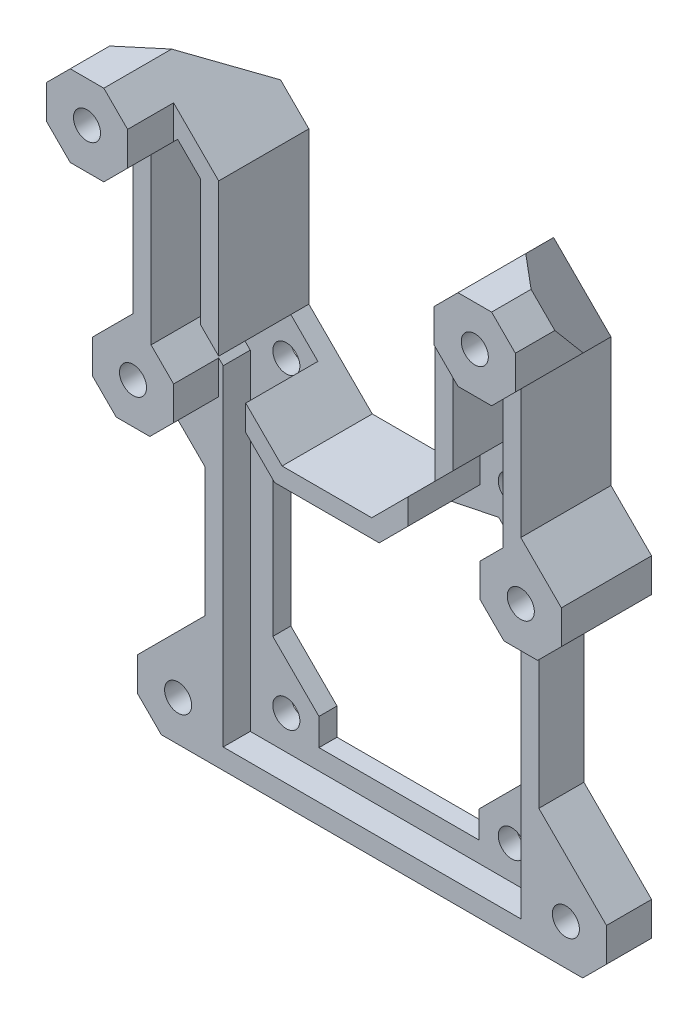
SolidWorks part; units mm, degrees
ref_plane "Front Plane" through (0, 0, 0) normal (0, 0, 1) x (1, 0, 0)
ref_plane "Top Plane" through (0, 0, 0) normal (0, 1, 0) x (1, 0, 0)
ref_plane "Right Plane" through (0, 0, 0) normal (1, 0, 0) x (0, 0, -1)
sketch "Sketch1" plane through (0, 0, 0) normal (0, 0, 1) x (1, 0, 0)
  line L0 (-21.5, 0) -> (21.5, 0) construction
  line L1 (21.5, 0) -> (21.5, 60) construction
  line L2 (21.5, 60) -> (-21.5, 60) construction
  line L3 (-21.5, 60) -> (-21.5, 0) construction
  line L4 (-21.5, 33) -> (21.5, 33) construction
  line L5 (0, 0) -> (0, 60) construction
  line L6 (-14, -2.1213) -> (-11, -2.1213)
  line L7 (-8.8787, 0) -> (-8.8787, 3)
  line L8 (-8.8787, 3) -> (-11, 5.1213)
  line L9 (-11, 5.1213) -> (-14, 5.1213)
  line L10 (-14, 5.1213) -> (-16.1213, 3)
  line L11 (-16.1213, 3) -> (-16.1213, 0)
  line L12 (-16.1213, 0) -> (-14, -2.1213)
  line L13 (-11, -2.1213) -> (-8.8787, 0)
  line L14 (-4.9706, 33) -> (-21.5, 49.5294) construction
  line L15 (8.8787, 0) -> (11, -2.1213)
  line L16 (11, -2.1213) -> (14, -2.1213)
  line L17 (14, -2.1213) -> (16.1213, 0)
  line L18 (16.1213, 0) -> (16.1213, 3)
  line L19 (16.1213, 3) -> (14, 5.1213)
  line L20 (14, 5.1213) -> (11, 5.1213)
  line L21 (11, 5.1213) -> (8.8787, 3)
  line L22 (8.8787, 3) -> (8.8787, 0)
  line L23 (-9, 34.1299) -> (-9, 37.0294)
  line L24 (-9, 37.0294) -> (-11.0503, 39.0797)
  line L25 (-11.0503, 39.0797) -> (-13.9497, 39.0797)
  line L26 (-13.9497, 39.0797) -> (-16, 37.0294)
  line L27 (-16, 37.0294) -> (-16, 34.1299)
  line L28 (-16, 34.1299) -> (-13.9497, 32.0797)
  line L29 (-13.9497, 32.0797) -> (-11.0503, 32.0797)
  line L30 (-11.0503, 32.0797) -> (-9, 34.1299)
  line L31 (9, 34.1299) -> (11.0503, 32.0797)
  line L32 (11.0503, 32.0797) -> (13.9497, 32.0797)
  line L33 (13.9497, 32.0797) -> (16, 34.1299)
  line L34 (16, 34.1299) -> (16, 37.0294)
  line L35 (16, 37.0294) -> (13.9497, 39.0797)
  line L36 (13.9497, 39.0797) -> (11.0503, 39.0797)
  line L37 (11.0503, 39.0797) -> (9, 37.0294)
  line L38 (9, 37.0294) -> (9, 34.1299)
  line L39 (-14, 0) -> (-14, 42.0294) construction
  line L40 (-16.5, 0) -> (-16.5, 44.5294) construction
  line L41 (-17, 58.136) -> (-17, 61.864)
  line L42 (-17, 61.864) -> (-19.636, 64.5)
  line L43 (-19.636, 64.5) -> (-23.364, 64.5)
  line L44 (-23.364, 64.5) -> (-26, 61.864)
  line L45 (-26, 61.864) -> (-26, 58.136)
  line L46 (-26, 58.136) -> (-23.364, 55.5)
  line L47 (-23.364, 55.5) -> (-19.636, 55.5)
  line L48 (-19.636, 55.5) -> (-17, 58.136)
  line L49 (-23.364, 37.5) -> (-26, 34.864)
  line L50 (-26, 34.864) -> (-26, 31.136)
  line L51 (-26, 31.136) -> (-23.364, 28.5)
  line L52 (-23.364, 28.5) -> (-19.636, 28.5)
  line L53 (-19.636, 28.5) -> (-17, 31.136)
  line L54 (-17, 31.136) -> (-17, 34.864)
  line L55 (-17, 34.864) -> (-19.636, 37.5)
  line L56 (-19.636, 37.5) -> (-23.364, 37.5)
  line L57 (-23.364, 4.5) -> (-26, 1.864)
  line L58 (-26, 1.864) -> (-26, -1.864)
  line L59 (-26, -1.864) -> (-23.364, -4.5)
  line L60 (-23.364, -4.5) -> (-19.636, -4.5)
  line L61 (-19.636, -4.5) -> (-17, -1.864)
  line L62 (-17, -1.864) -> (-17, 1.864)
  line L63 (-17, 1.864) -> (-19.636, 4.5)
  line L64 (-19.636, 4.5) -> (-23.364, 4.5)
  line L65 (23.364, -4.5) -> (26, -1.864)
  line L66 (26, -1.864) -> (26, 1.864)
  line L67 (26, 1.864) -> (23.364, 4.5)
  line L68 (23.364, 4.5) -> (19.636, 4.5)
  line L69 (19.636, 4.5) -> (17, 1.864)
  line L70 (17, 1.864) -> (17, -1.864)
  line L71 (17, -1.864) -> (19.636, -4.5)
  line L72 (19.636, -4.5) -> (23.364, -4.5)
  line L73 (19.636, 28.5) -> (23.364, 28.5)
  line L74 (23.364, 28.5) -> (26, 31.136)
  line L75 (26, 31.136) -> (26, 34.864)
  line L76 (26, 34.864) -> (23.364, 37.5)
  line L77 (23.364, 37.5) -> (19.636, 37.5)
  line L78 (19.636, 37.5) -> (17, 34.864)
  line L79 (17, 34.864) -> (17, 31.136)
  line L80 (17, 31.136) -> (19.636, 28.5)
  line L81 (23.364, 64.5) -> (19.636, 64.5)
  line L82 (19.636, 64.5) -> (17, 61.864)
  line L83 (17, 61.864) -> (17, 58.136)
  line L84 (17, 58.136) -> (19.636, 55.5)
  line L85 (19.636, 55.5) -> (23.364, 55.5)
  line L86 (23.364, 55.5) -> (26, 58.136)
  line L87 (26, 58.136) -> (26, 61.864)
  line L88 (26, 61.864) -> (23.364, 64.5)
  line L89 (-12, 45) -> (-12, 71.0139) construction
  line L90 (12, 45) -> (12, 71.0139) construction
  line L91 (0, -4.5) -> (-19.636, -4.5)
  line L92 (0, 0) -> (-8.8787, 0)
  line L94 (0, -2.25) -> (-16.5, -2.25)
  line L95 (-16.5, -2.25) -> (-16.5, 34.364)
  line L96 (-9, 37.0294) -> (-4.9706, 33)
  line L97 (0, -4.5) -> (0, 0) construction
  line L98 (0, 33) -> (-4.9706, 33)
  line L100 (-5.799, 31) -> (0, 31)
  line L101 (0, -2.25) -> (-16.5, -2.25) construction
  line L102 (-17, 61.864) -> (-12, 56.864)
  line L103 (-12, 56.864) -> (-12, 40.0294)
  line L104 (-12, 40.0294) -> (-11.0503, 39.0797)
  line L105 (-11.0503, 39.0797) -> (-12, 40.0294)
  line L106 (-23.364, 55.5) -> (-21.5, 53.636)
  line L107 (-23.364, 37.5) -> (-21.5, 39.364)
  line L108 (-21.5, 39.364) -> (-21.5, 53.636)
  line L109 (-23.364, 4.5) -> (-18.5, 9.364)
  line L110 (-18.5, 9.364) -> (-18.5, 23.636)
  line L111 (-18.5, 23.636) -> (-23.364, 28.5)
  line L112 (-11.0503, 32.0797) -> (-14, 29.1299)
  line L113 (-14, 29.1299) -> (-14, 8.1213)
  line L114 (-14, 8.1213) -> (-11, 5.1213)
  line L115 (-16.5, -4.5) -> (-16.5, 0) construction
  line L116 (-16.5503, 58.5858) -> (-14, 56.0355)
  line L117 (-14, 56.0355) -> (-14, 42.0294)
  line L118 (-14, 42.0294) -> (-12, 40.0294)
  line L119 (-17, 34.864) -> (-16.5, 34.364)
  line L120 (-19.636, 37.5) -> (-19.5, 37.364)
  line L121 (-19.5, 37.364) -> (-19.5, 55.636)
  line L122 (-19.5, 55.636) -> (-19.636, 55.5)
  line L123 (-17, 58.136) -> (-16.5503, 58.5858)
  line L124 (-19.636, 55.5) -> (-19.5, 55.636)
  line L125 (-9, 34.201) -> (-5.799, 31)
  line L126 (-9, 34.1299) -> (-8.9645, 34.1655)
  line L127 (-11.0503, 32.0797) -> (-5.799, 31)
  line L128 (-12, 50.5) -> (-33.4283, 71.9283) construction
  circle A0 centre (-21.5, 60) radius 1.5
  circle A1 centre (-21.5, 33) radius 1.5
  circle A2 centre (-21.5, 0) radius 1.5
  circle A3 centre (21.5, 0) radius 1.5
  circle A4 centre (21.5, 33) radius 1.5
  circle A5 centre (21.5, 60) radius 1.5
  circle A6 centre (-12.5, 1.5) radius 1.5
  circle A7 centre (12.5, 1.5) radius 1.5
  circle A8 centre (-12.5, 35.5797) radius 1.5
  circle A9 centre (12.5, 35.5797) radius 1.5
  circle A10 centre (0, 45) radius 12 construction
  circle A11 centre (-12.5, 1.5) radius 3.6213 construction
  circle A12 centre (12.5, 1.5) radius 3.6213 construction
  circle A13 centre (-12.5, 35.5797) radius 3.5 construction
  circle A14 centre (12.5, 35.5797) radius 3.5 construction
  circle A15 centre (-21.5, 60) radius 4.5 construction
  circle A16 centre (-21.5, 33) radius 4.5 construction
  circle A17 centre (-21.5, 0) radius 4.5 construction
  circle A18 centre (21.5, 0) radius 4.5 construction
  circle A19 centre (21.5, 33) radius 4.5 construction
  circle A20 centre (21.5, 60) radius 4.5 construction
  dimension "D4" = 3
  dimension "D5" = 24
  dimension "D7" = 45
  dimension "D8" = 7
  dimension "D9" = 9
  dimension "D10" = 9
  dimension "D11" = 9
  dimension "D12" = 9
  dimension "D13" = 9
  dimension "D14" = 9
  dimension "D1" = 43
  dimension "D2" = 33
  dimension "D3" = 27
  dimension "D6" = 12.5
  dimension "D15" = 2.5
  dimension "D16" = 2
  dimension "D17" = 2
  dimension "D18" = 45
  dimension "D19" = 45
  dimension "D20" = 2.25
  dimension "D21" = 2
  dimension "D22" = 2
  dimension "D23" = 2
  dimension "D24" = 2
sketch "Sketch5" plane through (0, 0, 0) normal (0, 0, 1) x (1, 0, 0)
  line L0 (0, -4.5) -> (-19.636, -4.5) construction
  line L1 (-23.364, -4.5) -> (-19.636, -4.5) construction
  line L2 (-26, -1.864) -> (-23.364, -4.5) construction
  line L3 (-26, 1.864) -> (-26, -1.864) construction
  line L4 (-23.364, 4.5) -> (-26, 1.864) construction
  line L5 (-23.364, 4.5) -> (-18.5, 9.364) construction
  line L6 (-18.5, 9.364) -> (-18.5, 23.636) construction
  line L7 (-18.5, 23.636) -> (-23.364, 28.5) construction
  line L8 (-26, 31.136) -> (-23.364, 28.5) construction
  line L9 (-26, 34.864) -> (-26, 31.136) construction
  line L10 (-23.364, 37.5) -> (-26, 34.864) construction
  line L11 (-23.364, 37.5) -> (-21.5, 39.364) construction
  line L12 (-21.5, 39.364) -> (-21.5, 53.636) construction
  line L13 (-23.364, 55.5) -> (-21.5, 53.636) construction
  line L14 (-26, 58.136) -> (-23.364, 55.5) construction
  line L15 (-26, 61.864) -> (-26, 58.136) construction
  line L16 (-23.364, 64.5) -> (-26, 61.864) construction
  line L17 (-19.636, 64.5) -> (-23.364, 64.5) construction
  line L18 (-17, 61.864) -> (-19.636, 64.5) construction
  line L19 (-17, 61.864) -> (-12, 56.864) construction
  line L20 (-12, 56.864) -> (-12, 40.0294) construction
  line L21 (-12, 40.0294) -> (-11.0503, 39.0797) construction
  line L22 (-9, 37.0294) -> (-11.0503, 39.0797) construction
  line L23 (-9, 37.0294) -> (-4.9706, 33) construction
  line L24 (0, 33) -> (-4.9706, 33) construction
  line L25 (-5.799, 31) -> (0, 31) construction
  line L26 (-11.0503, 32.0797) -> (-5.799, 31) construction
  line L28 (-11.0503, 32.0797) -> (-14, 29.1299) construction
  line L29 (-14, 29.1299) -> (-14, 8.1213) construction
  line L30 (-14, 8.1213) -> (-11, 5.1213) construction
  line L31 (-8.8787, 3) -> (-11, 5.1213) construction
  line L32 (-8.8787, 0) -> (-8.8787, 3) construction
  line L33 (0, 0) -> (-8.8787, 0) construction
  line L34 (0, 0) -> (0, 60) construction
  line L35 (0, -4.5) -> (0, 0) construction
  line L36 (19.636, -4.5) -> (-19.636, -4.5)
  line L37 (-23.364, -4.5) -> (-19.636, -4.5)
  line L38 (-26, -1.864) -> (-23.364, -4.5)
  line L39 (-26, 1.864) -> (-26, -1.864)
  line L40 (-23.364, 4.5) -> (-26, 1.864)
  line L41 (-23.364, 4.5) -> (-18.5, 9.364)
  line L42 (-18.5, 9.364) -> (-18.5, 23.636)
  line L43 (-18.5, 23.636) -> (-23.364, 28.5)
  line L44 (-26, 31.136) -> (-23.364, 28.5)
  line L45 (-26, 34.864) -> (-26, 31.136)
  line L46 (-23.364, 37.5) -> (-26, 34.864)
  line L47 (-23.364, 37.5) -> (-21.5, 39.364)
  line L48 (-21.5, 39.364) -> (-21.5, 53.636)
  line L49 (-23.364, 55.5) -> (-21.5, 53.636)
  line L50 (-26, 58.136) -> (-23.364, 55.5)
  line L51 (-26, 61.864) -> (-26, 58.136)
  line L52 (-23.364, 64.5) -> (-26, 61.864)
  line L53 (-19.636, 64.5) -> (-23.364, 64.5)
  line L54 (-17, 61.864) -> (-19.636, 64.5)
  line L55 (-17, 61.864) -> (-12, 56.864)
  line L56 (-12, 56.864) -> (-12, 40.0294)
  line L57 (-12, 40.0294) -> (-11.0503, 39.0797)
  line L58 (-9, 37.0294) -> (-11.0503, 39.0797)
  line L59 (-9, 37.0294) -> (-4.9706, 33)
  line L60 (4.9706, 33) -> (-4.9706, 33)
  line L61 (-5.799, 31) -> (5.799, 31)
  line L63 (11.0503, 32.0797) -> (5.799, 31)
  line L64 (-11.0503, 32.0797) -> (-14, 29.1299)
  line L65 (-14, 29.1299) -> (-14, 8.1213)
  line L66 (-14, 8.1213) -> (-11, 5.1213)
  line L67 (-8.8787, 3) -> (-11, 5.1213)
  line L68 (-8.8787, 0) -> (-8.8787, 3)
  line L69 (8.8787, 0) -> (-8.8787, 0)
  line L70 (0, 0) -> (0, 60) construction
  line L71 (0, -4.5) -> (0, 0) construction
  line L72 (8.8787, 0) -> (8.8787, 3)
  line L73 (8.8787, 3) -> (11, 5.1213)
  line L74 (14, 8.1213) -> (11, 5.1213)
  line L75 (14, 29.1299) -> (14, 8.1213)
  line L76 (11.0503, 32.0797) -> (14, 29.1299)
  line L79 (9, 37.0294) -> (4.9706, 33)
  line L80 (9, 37.0294) -> (11.0503, 39.0797)
  line L81 (12, 40.0294) -> (11.0503, 39.0797)
  line L82 (12, 56.864) -> (12, 40.0294)
  line L83 (17, 61.864) -> (12, 56.864)
  line L84 (17, 61.864) -> (19.636, 64.5)
  line L85 (19.636, 64.5) -> (23.364, 64.5)
  line L86 (23.364, 64.5) -> (26, 61.864)
  line L87 (26, 61.864) -> (26, 58.136)
  line L88 (26, 58.136) -> (23.364, 55.5)
  line L89 (23.364, 55.5) -> (21.5, 53.636)
  line L90 (21.5, 39.364) -> (21.5, 53.636)
  line L91 (23.364, 37.5) -> (21.5, 39.364)
  line L92 (23.364, 37.5) -> (26, 34.864)
  line L93 (26, 34.864) -> (26, 31.136)
  line L94 (26, 31.136) -> (23.364, 28.5)
  line L95 (18.5, 23.636) -> (23.364, 28.5)
  line L96 (18.5, 9.364) -> (18.5, 23.636)
  line L97 (23.364, 4.5) -> (18.5, 9.364)
  line L98 (23.364, 4.5) -> (26, 1.864)
  line L99 (26, 1.864) -> (26, -1.864)
  line L100 (26, -1.864) -> (23.364, -4.5)
  line L101 (23.364, -4.5) -> (19.636, -4.5)
  line L106 (-11.0503, 32.0797) -> (-5.799, 31)
  circle A0 centre (-12.5, 35.5797) radius 1.5 construction
  circle A1 centre (-12.5, 1.5) radius 1.5 construction
  circle A2 centre (12.5, 1.5) radius 1.5 construction
  circle A3 centre (12.5, 35.5797) radius 1.5 construction
  circle A4 centre (-12.5, 35.5797) radius 1.5
  circle A5 centre (-12.5, 1.5) radius 1.5
  circle A6 centre (12.5, 1.5) radius 1.5
  circle A7 centre (12.5, 35.5797) radius 1.5
extrude "Boss-Extrude1" add sketch "Sketch5" along normal blind 2
sketch "Sketch9" plane through (0, 0, 2) normal (0, 0, 1) x (1, 0, 0)
  line L0 (0, -4.5) -> (-19.636, -4.5) construction
  line L1 (-23.364, -4.5) -> (-19.636, -4.5) construction
  line L2 (-26, -1.864) -> (-23.364, -4.5) construction
  line L3 (-26, 1.864) -> (-26, -1.864) construction
  line L4 (-23.364, 4.5) -> (-26, 1.864) construction
  line L5 (-23.364, 4.5) -> (-18.5, 9.364) construction
  line L6 (-18.5, 9.364) -> (-18.5, 23.636) construction
  line L7 (-18.5, 23.636) -> (-23.364, 28.5) construction
  line L8 (-26, 31.136) -> (-23.364, 28.5) construction
  line L9 (-26, 34.864) -> (-26, 31.136) construction
  line L10 (-23.364, 37.5) -> (-26, 34.864) construction
  line L11 (-23.364, 37.5) -> (-21.5, 39.364) construction
  line L12 (-21.5, 39.364) -> (-21.5, 53.636) construction
  line L13 (-23.364, 55.5) -> (-21.5, 53.636) construction
  line L14 (-26, 58.136) -> (-23.364, 55.5) construction
  line L15 (-26, 61.864) -> (-26, 58.136) construction
  line L16 (-23.364, 64.5) -> (-26, 61.864) construction
  line L17 (-19.636, 64.5) -> (-23.364, 64.5) construction
  line L18 (-17, 61.864) -> (-19.636, 64.5) construction
  line L19 (-17, 61.864) -> (-12, 56.864) construction
  line L20 (-12, 56.864) -> (-12, 40.0294) construction
  line L21 (-14, 42.0294) -> (-12, 40.0294) construction
  line L22 (-14, 56.0355) -> (-14, 42.0294) construction
  line L24 (-16.5, -2.25) -> (-16.5, 34.364) construction
  line L25 (0, -2.25) -> (-16.5, -2.25) construction
  line L26 (0, 33) -> (-4.9706, 33) construction
  line L30 (-5.799, 31) -> (0, 31) construction
  line L31 (0, 0) -> (0, 60) construction
  line L32 (0, -4.5) -> (0, 0) construction
  line L33 (19.636, -4.5) -> (-19.636, -4.5)
  line L34 (-23.364, -4.5) -> (-19.636, -4.5)
  line L35 (-26, -1.864) -> (-23.364, -4.5)
  line L36 (-26, 1.864) -> (-26, -1.864)
  line L37 (-23.364, 4.5) -> (-26, 1.864)
  line L38 (-23.364, 4.5) -> (-18.5, 9.364)
  line L39 (-18.5, 9.364) -> (-18.5, 23.636)
  line L40 (-18.5, 23.636) -> (-23.364, 28.5)
  line L41 (-26, 31.136) -> (-23.364, 28.5)
  line L42 (-26, 34.864) -> (-26, 31.136)
  line L43 (-23.364, 37.5) -> (-26, 34.864)
  line L44 (-23.364, 37.5) -> (-21.5, 39.364)
  line L45 (-21.5, 39.364) -> (-21.5, 53.636)
  line L46 (-23.364, 55.5) -> (-21.5, 53.636)
  line L47 (-26, 58.136) -> (-23.364, 55.5)
  line L48 (-26, 61.864) -> (-26, 58.136)
  line L49 (-23.364, 64.5) -> (-26, 61.864)
  line L50 (-19.636, 64.5) -> (-23.364, 64.5)
  line L51 (-17, 61.864) -> (-19.636, 64.5)
  line L52 (-17, 61.864) -> (-12, 56.864)
  line L53 (-12, 56.864) -> (-12, 40.0294)
  line L54 (-14, 42.0294) -> (-12, 40.0294)
  line L55 (-14, 56.0355) -> (-14, 42.0294)
  line L56 (-17, 34.864) -> (-16.5, 34.364) construction
  line L57 (-17, 34.864) -> (-19.636, 37.5) construction
  line L58 (16.5, -2.25) -> (-16.5, -2.25)
  line L59 (-9, 37.0294) -> (-4.9706, 33) construction
  line L60 (-9, 34.1299) -> (-9, 37.0294) construction
  line L62 (4.9706, 33) -> (-4.9706, 33)
  line L63 (-9, 37.0294) -> (-4.9706, 33)
  line L64 (0, 0) -> (0, 60) construction
  line L65 (0, -4.5) -> (0, 0) construction
  line L66 (19.636, 64.5) -> (23.364, 64.5)
  line L67 (-9, 34.201) -> (-9, 37.0294)
  line L68 (9, 34.201) -> (5.799, 31)
  line L69 (-5.799, 31) -> (5.799, 31)
  line L70 (16.5, -2.25) -> (16.5, 34.364)
  line L72 (14, 56.0355) -> (14, 42.0294)
  line L73 (14, 42.0294) -> (12, 40.0294)
  line L74 (12, 56.864) -> (12, 40.0294)
  line L75 (17, 61.864) -> (12, 56.864)
  line L76 (17, 61.864) -> (19.636, 64.5)
  line L77 (23.364, 64.5) -> (26, 61.864)
  line L78 (26, 61.864) -> (26, 58.136)
  line L79 (26, 58.136) -> (23.364, 55.5)
  line L80 (23.364, 55.5) -> (21.5, 53.636)
  line L81 (21.5, 39.364) -> (21.5, 53.636)
  line L82 (23.364, 37.5) -> (21.5, 39.364)
  line L83 (23.364, 37.5) -> (26, 34.864)
  line L84 (26, 34.864) -> (26, 31.136)
  line L85 (26, 31.136) -> (23.364, 28.5)
  line L86 (18.5, 23.636) -> (23.364, 28.5)
  line L87 (18.5, 9.364) -> (18.5, 23.636)
  line L88 (23.364, 4.5) -> (18.5, 9.364)
  line L89 (23.364, 4.5) -> (26, 1.864)
  line L90 (26, 1.864) -> (26, -1.864)
  line L91 (26, -1.864) -> (23.364, -4.5)
  line L92 (23.364, -4.5) -> (19.636, -4.5)
  line L93 (9, 34.201) -> (9, 37.0294)
  line L94 (17, 34.864) -> (16.5, 34.364)
  line L95 (9, 37.0294) -> (4.9706, 33)
  line L96 (-19.5, 37.364) -> (-19.5, 55.636) construction
  line L98 (-19.636, 55.5) -> (-17, 58.136) construction
  line L99 (-17, 58.136) -> (-16.5503, 58.5858) construction
  line L100 (-16.5503, 58.5858) -> (-14, 56.0355) construction
  line L101 (-9, 34.201) -> (-5.799, 31) construction
  line L102 (-16.5, -2.25) -> (-16.5, 34.364)
  line L103 (-17, 34.864) -> (-16.5, 34.364)
  line L104 (-17, 34.864) -> (-19.5, 37.364)
  line L106 (-19.5, 37.364) -> (-19.5, 55.636)
  line L108 (-19.5, 55.636) -> (-17, 58.136)
  line L109 (-17, 58.136) -> (-16.5503, 58.5858)
  line L110 (-16.5503, 58.5858) -> (-14, 56.0355)
  line L111 (-9, 34.201) -> (-5.799, 31)
  line L112 (17, 34.864) -> (19.5, 37.364)
  line L114 (19.5, 37.364) -> (19.5, 55.636)
  line L116 (19.5, 55.636) -> (17, 58.136)
  line L117 (17, 58.136) -> (16.5503, 58.5858)
  line L118 (16.5503, 58.5858) -> (14, 56.0355)
  circle A0 centre (-21.5, 0) radius 1.5 construction
  circle A1 centre (-21.5, 33) radius 1.5 construction
  circle A3 centre (-21.5, 0) radius 1.5
  circle A4 centre (-21.5, 33) radius 1.5
  circle A7 centre (21.5, 33) radius 1.5
  circle A8 centre (21.5, 0) radius 1.5
extrude "Boss-Extrude3" add sketch "Sketch9" along normal blind 3
sketch "Sketch10" plane through (0, 0, 5) normal (0, 0, 1) x (1, 0, 0)
  line L0 (-23.364, 28.5) -> (-19.636, 28.5) construction
  line L1 (-26, 31.136) -> (-23.364, 28.5) construction
  line L2 (-26, 34.864) -> (-26, 31.136) construction
  line L3 (-23.364, 37.5) -> (-26, 34.864) construction
  line L4 (-23.364, 37.5) -> (-21.5, 39.364) construction
  line L5 (-21.5, 39.364) -> (-21.5, 53.636) construction
  line L6 (-23.364, 55.5) -> (-21.5, 53.636) construction
  line L7 (-26, 58.136) -> (-23.364, 55.5) construction
  line L8 (-26, 61.864) -> (-26, 58.136) construction
  line L9 (-23.364, 64.5) -> (-26, 61.864) construction
  line L10 (-19.636, 64.5) -> (-23.364, 64.5) construction
  line L11 (-17, 61.864) -> (-19.636, 64.5) construction
  line L12 (-17, 61.864) -> (-12, 56.864) construction
  line L13 (-12, 56.864) -> (-12, 40.0294) construction
  line L14 (-14, 42.0294) -> (-12, 40.0294) construction
  line L15 (-14, 56.0355) -> (-14, 42.0294) construction
  line L16 (-16.5503, 58.5858) -> (-14, 56.0355) construction
  line L17 (-17, 58.136) -> (-16.5503, 58.5858) construction
  line L18 (-19.636, 55.5) -> (-17, 58.136) construction
  line L20 (-19.5, 37.364) -> (-19.5, 55.636) construction
  line L22 (-17, 34.864) -> (-19.636, 37.5) construction
  line L23 (-17, 31.136) -> (-17, 34.864) construction
  line L24 (-19.636, 28.5) -> (-17, 31.136) construction
  line L25 (-9, 34.1299) -> (-9, 37.0294) construction
  line L26 (-9, 37.0294) -> (-4.9706, 33) construction
  line L27 (0, 33) -> (-4.9706, 33) construction
  line L28 (-5.799, 31) -> (0, 31) construction
  line L29 (-9, 34.201) -> (-5.799, 31) construction
  line L30 (-23.364, 28.5) -> (-19.636, 28.5)
  line L31 (-26, 31.136) -> (-23.364, 28.5)
  line L32 (-26, 34.864) -> (-26, 31.136)
  line L33 (-23.364, 37.5) -> (-26, 34.864)
  line L34 (-23.364, 37.5) -> (-21.5, 39.364)
  line L35 (-21.5, 39.364) -> (-21.5, 53.636)
  line L36 (-23.364, 55.5) -> (-21.5, 53.636)
  line L37 (-26, 58.136) -> (-23.364, 55.5)
  line L38 (-26, 61.864) -> (-26, 58.136)
  line L39 (-23.364, 64.5) -> (-26, 61.864)
  line L40 (-19.636, 64.5) -> (-23.364, 64.5)
  line L41 (-17, 61.864) -> (-19.636, 64.5)
  line L42 (-17, 61.864) -> (-12, 56.864)
  line L43 (-12, 56.864) -> (-12, 40.0294)
  line L44 (-14, 42.0294) -> (-12, 40.0294)
  line L45 (-14, 56.0355) -> (-14, 42.0294)
  line L46 (-16.5503, 58.5858) -> (-14, 56.0355)
  line L47 (-17, 58.136) -> (-16.5503, 58.5858)
  line L48 (-19.5, 55.636) -> (-17, 58.136)
  line L50 (-19.5, 37.364) -> (-19.5, 55.636)
  line L52 (-17, 34.864) -> (-19.5, 37.364)
  line L53 (-17, 31.136) -> (-17, 34.864)
  line L54 (-19.636, 28.5) -> (-17, 31.136)
  line L55 (-9, 34.201) -> (-9, 37.0294)
  line L56 (-9, 37.0294) -> (-4.9706, 33)
  line L57 (4.9706, 33) -> (-4.9706, 33)
  line L58 (-5.799, 31) -> (5.799, 31)
  line L59 (-9, 34.201) -> (-5.799, 31)
  line L60 (0, 0) -> (0, 60) construction
  line L61 (0, 0) -> (0, 60) construction
  line L62 (9, 34.201) -> (5.799, 31)
  line L63 (9, 37.0294) -> (4.9706, 33)
  line L64 (9, 34.201) -> (9, 37.0294)
  line L65 (19.636, 28.5) -> (17, 31.136)
  line L66 (17, 31.136) -> (17, 34.864)
  line L67 (17, 34.864) -> (19.5, 37.364)
  line L69 (19.5, 37.364) -> (19.5, 55.636)
  line L71 (19.5, 55.636) -> (17, 58.136)
  line L72 (17, 58.136) -> (16.5503, 58.5858)
  line L73 (16.5503, 58.5858) -> (14, 56.0355)
  line L74 (14, 56.0355) -> (14, 42.0294)
  line L75 (14, 42.0294) -> (12, 40.0294)
  line L76 (12, 56.864) -> (12, 40.0294)
  line L77 (17, 61.864) -> (12, 56.864)
  line L78 (17, 61.864) -> (19.636, 64.5)
  line L79 (19.636, 64.5) -> (23.364, 64.5)
  line L80 (23.364, 64.5) -> (26, 61.864)
  line L81 (26, 61.864) -> (26, 58.136)
  line L82 (26, 58.136) -> (23.364, 55.5)
  line L83 (23.364, 55.5) -> (21.5, 53.636)
  line L84 (21.5, 39.364) -> (21.5, 53.636)
  line L85 (23.364, 37.5) -> (21.5, 39.364)
  line L86 (23.364, 37.5) -> (26, 34.864)
  line L87 (26, 34.864) -> (26, 31.136)
  line L88 (26, 31.136) -> (23.364, 28.5)
  line L89 (23.364, 28.5) -> (19.636, 28.5)
  circle A0 centre (-21.5, 33) radius 1.5 construction
  circle A2 centre (-21.5, 33) radius 1.5
  circle A5 centre (21.5, 33) radius 1.5
extrude "Boss-Extrude4" add sketch "Sketch10" along normal blind 5
sketch "Sketch12" plane through (0, 0, 10) normal (0, 0, 1) x (1, 0, 0)
  line L0 (-26, 58.136) -> (-23.364, 55.5) construction
  line L1 (-26, 61.864) -> (-26, 58.136) construction
  line L2 (-23.364, 64.5) -> (-26, 61.864) construction
  line L3 (-19.636, 64.5) -> (-23.364, 64.5) construction
  line L4 (-17, 61.864) -> (-19.636, 64.5) construction
  line L5 (-17, 58.136) -> (-17, 61.864) construction
  line L6 (-19.636, 55.5) -> (-17, 58.136) construction
  line L7 (-23.364, 55.5) -> (-19.636, 55.5) construction
  line L8 (-26, 58.136) -> (-23.364, 55.5)
  line L9 (-26, 61.864) -> (-26, 58.136)
  line L10 (-23.364, 64.5) -> (-26, 61.864)
  line L11 (-19.636, 64.5) -> (-23.364, 64.5)
  line L12 (-17, 61.864) -> (-19.636, 64.5)
  line L13 (-17, 58.136) -> (-17, 61.864)
  line L14 (-19.636, 55.5) -> (-17, 58.136)
  line L15 (-23.364, 55.5) -> (-19.636, 55.5)
  line L16 (0, 0) -> (0, 60) construction
  line L17 (0, 0) -> (0, 60) construction
  line L18 (17, 58.136) -> (17, 61.864)
  line L19 (17, 61.864) -> (19.636, 64.5)
  line L20 (19.636, 64.5) -> (23.364, 64.5)
  line L21 (23.364, 64.5) -> (26, 61.864)
  line L22 (26, 61.864) -> (26, 58.136)
  line L23 (26, 58.136) -> (23.364, 55.5)
  line L24 (23.364, 55.5) -> (19.636, 55.5)
  line L25 (19.636, 55.5) -> (17, 58.136)
extrude "Boss-Extrude5" add sketch "Sketch12" along normal blind 5.1
ref_plane "Plane1" through (19.25, 19.25, 0) normal (0.7071, 0.7071, 0) x (0, 0, -1)
ref_plane "Plane2" through (-19.25, 19.25, 0) normal (-0.7071, 0.7071, 0) x (0.7071, 0.7071, 0)
sketch "Sketch13" plane through (0, 0, 15.1) normal (0, 0, 1) x (1, 0, 0)
  line L0 (0, 0) -> (0, 60) construction
  line L1 (0, 0) -> (0, 60) construction
  circle A0 centre (-21.5, 60) radius 1.5 construction
  circle A1 centre (-21.5, 60) radius 1.5
  circle A2 centre (21.5, 60) radius 1.5
extrude "Cut-Extrude1" cut sketch "Sketch13" against normal blind 4.5
sketch "Sketch15" plane through (19.25, 19.25, 0) normal (0.7071, 0.7071, 0) x (0, 0, -1)
  line L0 (0, 53.1292) -> (-15.3209, 65.985)
  line L1 (-15.3209, 65.985) -> (-8.893, 73.6454)
  line L2 (-8.893, 73.6454) -> (6.4279, 60.7896)
  line L3 (6.4279, 60.7896) -> (0, 53.1292)
  line L4 (0, 44.1942) -> (0, 74.4983) construction
  dimension "D1" = 20
  dimension "D2" = 10
  dimension "D3" = 50
extrude "Cut-Extrude2" cut sketch "Sketch15" against normal mid plane 15
sketch "Sketch16" plane through (-19.25, 19.25, 0) normal (-0.7071, 0.7071, 0) x (0.7071, 0.7071, 0)
  line L0 (53.1292, 0) -> (65.985, -15.3209)
  line L1 (65.985, -15.3209) -> (73.6454, -8.893)
  line L2 (73.6454, -8.893) -> (60.7896, 6.4279)
  line L3 (60.7896, 6.4279) -> (53.1292, 0)
  line L4 (59.4932, 0) -> (48.6942, 0) construction
  dimension "D1" = 50
  dimension "D2" = 20
  dimension "D3" = 10
extrude "Cut-Extrude3" cut sketch "Sketch16" against normal mid plane 15
chamfer "Chamfer1" distance 1 angle 50 2 edges at (-18.0251, 57.1109, 2) (18.0251, 57.1109, 2) first distance on face at (14, 1.5, 2)
